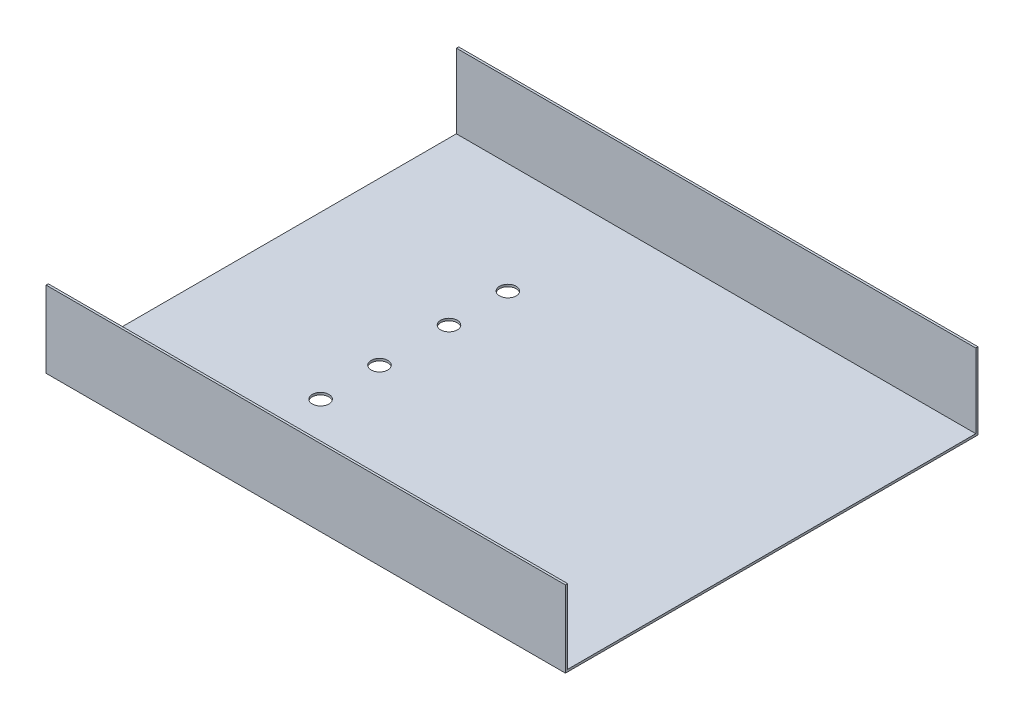
SolidWorks part; units mm, degrees
material "AISI 304"
ref_plane "Alzado" through (0, 0, 0) normal (0, 0, 1) x (1, 0, 0)
ref_plane "Planta" through (0, 0, 0) normal (0, 1, 0) x (1, 0, 0)
ref_plane "Vista lateral" through (0, 0, 0) normal (1, 0, 0) x (0, 0, -1)
sketch "Croquis1" plane through (0, 0, 0) normal (1, 0, 0) x (0, 0, -1)
  line L0 (0, 20) -> (0, 0)
  line L1 (0, 0) -> (110, 0)
  line L2 (110, 0) -> (110, 20)
  line L3 (0, 20) -> (110, 20)
  dimension "D1" = 110
  dimension "D2" = 20
extrude "Saliente-Extruir1" add sketch "Croquis1" along normal blind 140
shell "Vaciado1" thickness 0.6 removed face at (0, 10, -55) removed face at (140, 10, -55) removed face at (70, 20, -55) outward yes
hole_wizard "Taladro de margen para M42" positions "Croquis4" profile "Croquis5" hole size "M4" standard "Ansi Metric"
sketch "Croquis4" plane through (104.2341, 1, -171.2) normal (0, 1, 0) x (1, 0, 0)
  point P0 (-60.5841, -90.9625)
  point P5 (-60.5841, -106.8375)
  point P8 (-60.5841, -125.5625)
  point P11 (-60.5841, -141.4375)
sketch "Croquis5" plane through (43.65, 1, -80.2375) normal (1, 0, 0) x (0, 0, 1)
  line L0 (0, 0) -> (0, 1.599)
  line L1 (0, 1.599) -> (2.25, 1.599)
  line L2 (2.25, 1.599) -> (2.25, 0)
  line L3 (2.25, 0) -> (0, 0)
  line L4 (0, -6.35) -> (0, 107.95) construction
  dimension "Diámetro de taladro hasta el siguiente" = 4.5
  dimension "Profundidad de taladro hasta el siguiente" = 1.599
